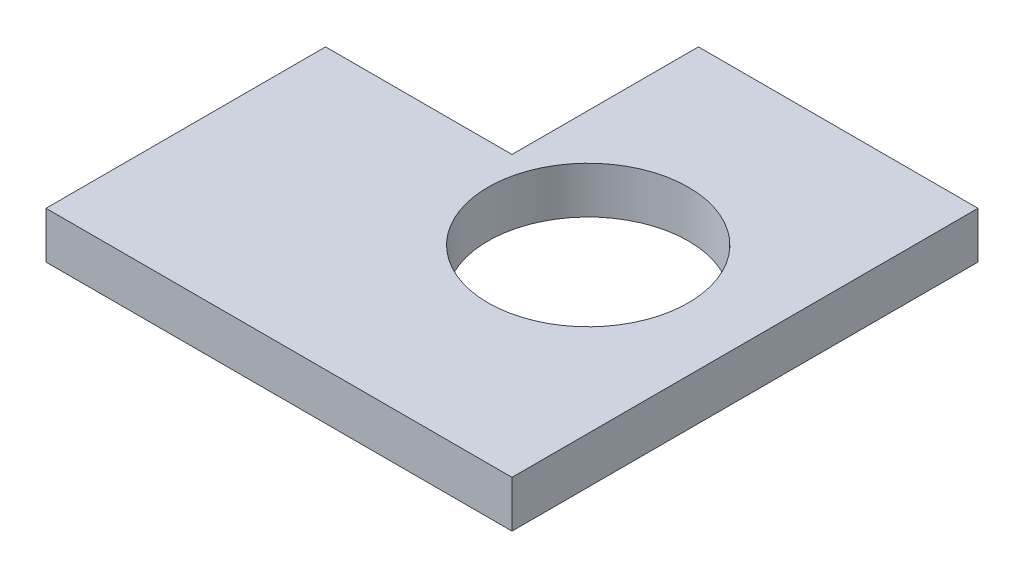
SolidWorks part; units mm, degrees
ref_plane "Спереди" through (0, 0, 0) normal (0, 0, 1) x (1, 0, 0)
ref_plane "Сверху" through (0, 0, 0) normal (0, 1, 0) x (1, 0, 0)
ref_plane "Справа" through (0, 0, 0) normal (1, 0, 0) x (0, 0, -1)
sketch "Эскиз1" plane through (0, 0, 0) normal (0, 1, 0) x (1, 0, 0)
  line L0 (0, 0) -> (100, 0)
  line L1 (100, 0) -> (100, 100)
  line L2 (100, 100) -> (40, 100)
  line L3 (40, 100) -> (40, 60)
  line L4 (40, 60) -> (0, 60)
  line L5 (0, 60) -> (0, 0)
  circle A0 centre (65, 51.3519) radius 21.5
  point P8 (65, 51.3519)
extrude "Бобышка-Вытянуть1" add sketch "Эскиз1" along normal blind 10
